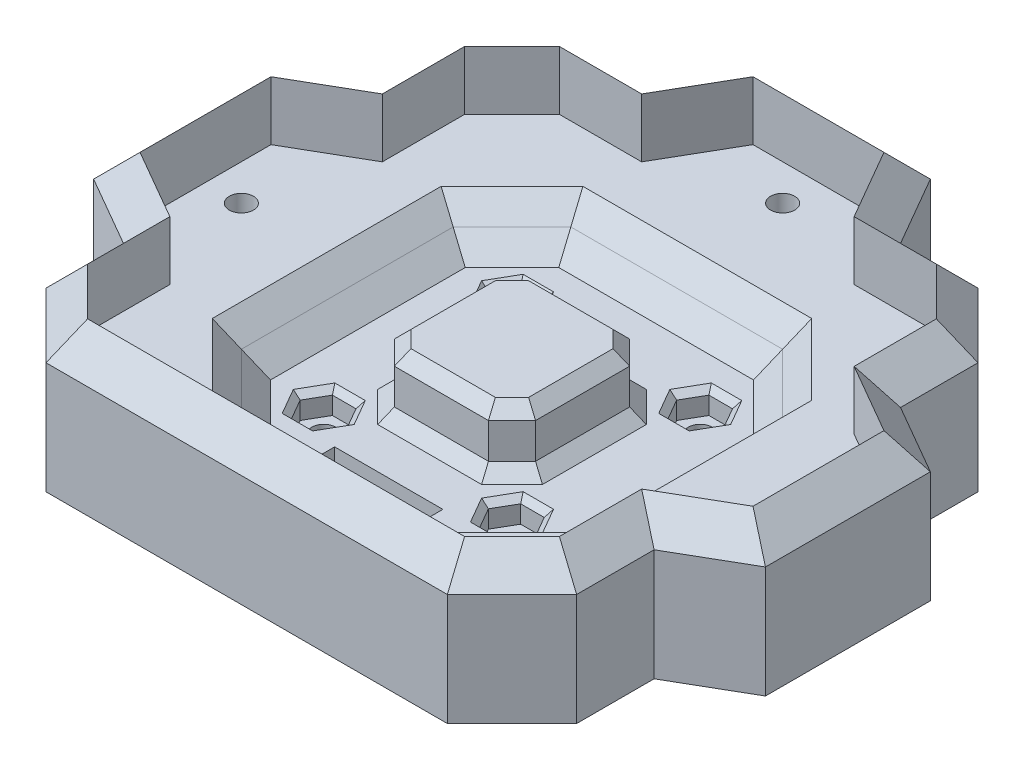
SolidWorks part; units mm, degrees
material "ABS"
ref_plane "Front Plane" through (0, 0, 0) normal (0, 0, 1) x (1, 0, 0)
ref_plane "Top Plane" through (0, 0, 0) normal (0, 1, 0) x (1, 0, 0)
ref_plane "Right Plane" through (0, 0, 0) normal (1, 0, 0) x (0, 0, -1)
sketch "Track Reference" plane through (0, 0, 0) normal (0, 1, 0) x (1, 0, 0)
  line L0 (-40, 32) -> (-32, 40)
  line L1 (-32, 40) -> (-18, 40)
  line L2 (-40, 32) -> (-40, 18)
  line L3 (-32, -40) -> (-5, -40)
  line L4 (40, 32) -> (40, 18)
  line L5 (-40, -32) -> (-32, -40)
  line L6 (32, -40) -> (40, -32)
  line L7 (32, 40) -> (40, 32)
  line L8 (-40, -18) -> (-52, -11.0718)
  line L9 (-52, -11.0718) -> (-52, 11.0718)
  line L10 (-52, 11.0718) -> (-40, 18)
  line L11 (-18, 40) -> (-11.0718, 52)
  line L12 (-11.0718, 52) -> (11.0718, 52)
  line L13 (11.0718, 52) -> (18, 40)
  line L14 (40, 18) -> (52, 11.0718)
  line L15 (52, 11.0718) -> (52, -11.0718)
  line L16 (52, -11.0718) -> (40, -18)
  line L17 (18, -40) -> (11.0718, -52)
  line L18 (11.0718, -52) -> (-11.0718, -52)
  line L19 (-11.0718, -52) -> (-18, -40)
  line L20 (-5, -27.65) -> (-5, -40)
  line L21 (-5, -27.65) -> (-9, -23.65)
  line L22 (-9, -23.65) -> (-9, -21.15)
  line L23 (-9, -21.15) -> (9, -21.15)
  line L24 (9, -21.15) -> (9, -23.65)
  line L25 (9, -23.65) -> (5, -27.65)
  line L26 (5, -27.65) -> (5, -40)
  line L27 (-40, 18) -> (-40, -18) construction
  line L28 (-40, -18) -> (-40, -32)
  line L29 (-18, 40) -> (18, 40) construction
  line L30 (18, 40) -> (32, 40)
  line L31 (40, 18) -> (40, -18) construction
  line L32 (40, -18) -> (40, -32)
  line L33 (-5, -40) -> (5, -40) construction
  line L34 (5, -40) -> (32, -40)
  circle A0 centre (-46, 0) radius 2.05
  circle A1 centre (0, 46) radius 2.05
  circle A2 centre (46, 0) radius 2.05
  circle A3 centre (0, -46) radius 2.05
  point P0 (-40, 40)
  point P1 (40, -40)
  point P2 (-40, -40)
  point P3 (40, 40)
  point P14 (-52, 0)
  point P22 (0, -21.15)
  point P23 (0, 0)
  point P25 (0, 0)
  point P44 (0, 0)
  point P51 (0, 0)
  point P52 (9, -19.8212)
  dimension "D8" = 4.1
  dimension "D1" = 80
  dimension "D2" = 80
  dimension "D3" = 8
  dimension "D4" = 8
  dimension "D5" = 60
  dimension "D6" = 12
  dimension "D7" = 36
  dimension "D9" = 6
  dimension "D12" = 18
  dimension "D11" = 10
  dimension "D13" = 2.5
  dimension "D14" = 45
  dimension "D15" = 18.85
  dimension "D10" = 4
sketch "Sketch2" plane through (0, 0, 0) normal (0, 1, 0) x (1, 0, 0)
  line L127 (-5, -40.1) -> (5, -40.1)
  line L128 (-5, -45.1) -> (5, -45.1)
  line L129 (5, -45.1) -> (34.1125, -45.1)
  line L130 (34.1125, -45.1) -> (45.1, -34.1125)
  line L131 (45.1, -34.1125) -> (45.1, -20.9445)
  line L132 (45.1, -20.9445) -> (57.1, -14.0163)
  line L133 (57.1, -14.0163) -> (57.1, 14.0163)
  line L134 (57.1, 14.0163) -> (45.1, 20.9445)
  line L135 (45.1, 20.9445) -> (45.1, 34.1125)
  line L136 (45.1, 34.1125) -> (34.1125, 45.1)
  line L137 (34.1125, 45.1) -> (20.9445, 45.1)
  line L138 (20.9445, 45.1) -> (14.0163, 57.1)
  line L139 (14.0163, 57.1) -> (-14.0163, 57.1)
  line L140 (-14.0163, 57.1) -> (-20.9445, 45.1)
  line L141 (-20.9445, 45.1) -> (-34.1125, 45.1)
  line L142 (-34.1125, 45.1) -> (-45.1, 34.1125)
  line L143 (-45.1, 34.1125) -> (-45.1, 20.9445)
  line L144 (-45.1, 20.9445) -> (-57.1, 14.0163)
  line L145 (-57.1, 14.0163) -> (-57.1, -14.0163)
  line L146 (-57.1, -14.0163) -> (-45.1, -20.9445)
  line L147 (-45.1, -20.9445) -> (-45.1, -34.1125)
  line L148 (11.1295, 52.1) -> (-11.1295, 52.1)
  line L149 (18.0577, 40.1) -> (11.1295, 52.1)
  line L150 (32.0414, 40.1) -> (18.0577, 40.1)
  line L151 (40.1, 32.0414) -> (32.0414, 40.1)
  line L152 (40.1, 18.0577) -> (40.1, 32.0414)
  line L153 (52.1, 11.1295) -> (40.1, 18.0577)
  line L154 (52.1, -11.1295) -> (52.1, 11.1295)
  line L155 (40.1, -18.0577) -> (52.1, -11.1295)
  line L156 (40.1, -32.0414) -> (40.1, -18.0577)
  line L157 (32.0414, -40.1) -> (40.1, -32.0414)
  line L158 (5, -40.1) -> (32.0414, -40.1)
  line L159 (-32.0414, -40.1) -> (-5, -40.1)
  line L160 (-40.1, -32.0414) -> (-32.0414, -40.1)
  line L161 (-40.1, -18.0577) -> (-40.1, -32.0414)
  line L162 (-52.1, -11.1295) -> (-40.1, -18.0577)
  line L163 (-52.1, 11.1295) -> (-52.1, -11.1295)
  line L164 (-40.1, 18.0577) -> (-52.1, 11.1295)
  line L165 (-40.1, 32.0414) -> (-40.1, 18.0577)
  line L166 (-32.0414, 40.1) -> (-40.1, 32.0414)
  line L167 (-18.0577, 40.1) -> (-32.0414, 40.1)
  line L168 (-11.1295, 52.1) -> (-18.0577, 40.1)
  line L169 (11.1295, 52.1) -> (-11.1295, 52.1)
  line L170 (18.0577, 40.1) -> (11.1295, 52.1)
  line L171 (32.0414, 40.1) -> (18.0577, 40.1)
  line L172 (40.1, 32.0414) -> (32.0414, 40.1)
  line L173 (40.1, 18.0577) -> (40.1, 32.0414)
  line L174 (52.1, 11.1295) -> (40.1, 18.0577)
  line L175 (52.1, -11.1295) -> (52.1, 11.1295)
  line L176 (40.1, -18.0577) -> (52.1, -11.1295)
  line L177 (40.1, -32.0414) -> (40.1, -18.0577)
  line L178 (32.0414, -40.1) -> (40.1, -32.0414)
  line L179 (5, -40.1) -> (32.0414, -40.1)
  line L180 (-32.0414, -40.1) -> (-5, -40.1)
  line L181 (-40.1, -32.0414) -> (-32.0414, -40.1)
  line L182 (-40.1, -18.0577) -> (-40.1, -32.0414)
  line L183 (-52.1, -11.1295) -> (-40.1, -18.0577)
  line L184 (-52.1, 11.1295) -> (-52.1, -11.1295)
  line L185 (-40.1, 18.0577) -> (-52.1, 11.1295)
  line L186 (-40.1, 32.0414) -> (-40.1, 18.0577)
  line L187 (-32.0414, 40.1) -> (-40.1, 32.0414)
  line L188 (-18.0577, 40.1) -> (-32.0414, 40.1)
  line L189 (-11.1295, 52.1) -> (-18.0577, 40.1)
  line L190 (-45.1, -34.1125) -> (-34.1125, -45.1)
  line L191 (-34.1125, -45.1) -> (-5, -45.1)
  dimension "D1" = 0.1
  dimension "D2" = 5
extrude "Outer Walls Extrude" add sketch "Sketch2" along normal blind 10
sketch "Sketch3" plane through (0, 0, 0) normal (0, -1, 0) x (1, 0, 0)
  line L20 (34.1125, 45.1) -> (-34.1125, 45.1)
  line L21 (-34.1125, 45.1) -> (-45.1, 34.1125)
  line L22 (-45.1, 34.1125) -> (-45.1, 20.9445)
  line L23 (-45.1, 20.9445) -> (-57.1, 14.0163)
  line L24 (-57.1, 14.0163) -> (-57.1, -14.0163)
  line L25 (-57.1, -14.0163) -> (-45.1, -20.9445)
  line L26 (-45.1, -20.9445) -> (-45.1, -34.1125)
  line L27 (-45.1, -34.1125) -> (-34.1125, -45.1)
  line L28 (-34.1125, -45.1) -> (-20.9445, -45.1)
  line L29 (-20.9445, -45.1) -> (-14.0163, -57.1)
  line L30 (-14.0163, -57.1) -> (14.0163, -57.1)
  line L31 (14.0163, -57.1) -> (20.9445, -45.1)
  line L32 (20.9445, -45.1) -> (34.1125, -45.1)
  line L33 (34.1125, -45.1) -> (45.1, -34.1125)
  line L34 (45.1, -34.1125) -> (45.1, -20.9445)
  line L35 (45.1, -20.9445) -> (57.1, -14.0163)
  line L36 (57.1, -14.0163) -> (57.1, 14.0163)
  line L37 (57.1, 14.0163) -> (45.1, 20.9445)
  line L38 (45.1, 20.9445) -> (45.1, 34.1125)
  line L39 (45.1, 34.1125) -> (34.1125, 45.1)
  line L40 (34.1125, 45.1) -> (-34.1125, 45.1)
  line L41 (-34.1125, 45.1) -> (-45.1, 34.1125)
  line L42 (-45.1, 34.1125) -> (-45.1, 20.9445)
  line L43 (-45.1, 20.9445) -> (-57.1, 14.0163)
  line L44 (-57.1, 14.0163) -> (-57.1, -14.0163)
  line L45 (-57.1, -14.0163) -> (-45.1, -20.9445)
  line L46 (-45.1, -20.9445) -> (-45.1, -34.1125)
  line L47 (-45.1, -34.1125) -> (-34.1125, -45.1)
  line L48 (-34.1125, -45.1) -> (-20.9445, -45.1)
  line L49 (-20.9445, -45.1) -> (-14.0163, -57.1)
  line L50 (-14.0163, -57.1) -> (14.0163, -57.1)
  line L51 (14.0163, -57.1) -> (20.9445, -45.1)
  line L52 (20.9445, -45.1) -> (34.1125, -45.1)
  line L53 (34.1125, -45.1) -> (45.1, -34.1125)
  line L54 (45.1, -34.1125) -> (45.1, -20.9445)
  line L55 (45.1, -20.9445) -> (57.1, -14.0163)
  line L56 (57.1, -14.0163) -> (57.1, 14.0163)
  line L57 (57.1, 14.0163) -> (45.1, 20.9445)
  line L58 (45.1, 20.9445) -> (45.1, 34.1125)
  line L59 (45.1, 34.1125) -> (34.1125, 45.1)
  dimension "D1" = 0
extrude "Base Extrude" add sketch "Sketch3" along normal blind 14
sketch "Sketch11" plane through (0, 0, 0) normal (0, 1, 0) x (1, 0, 0)
  line L15 (-5.2, -40) -> (-5.2, -40.1)
  line L16 (-32.0414, -40.1) -> (32.0414, -40.1) construction
  line L17 (5.2, -40) -> (5.2, -40.1)
  line L18 (5.2, -40.1) -> (-5.2, -40.1)
  line L22 (5.2, -40) -> (5.2, -27.7328)
  line L23 (5.2, -27.7328) -> (9.2, -23.7328)
  line L24 (9.2, -23.7328) -> (9.2, -20.95)
  line L25 (9.2, -20.95) -> (-9.2, -20.95)
  line L26 (-9.2, -20.95) -> (-9.2, -23.7328)
  line L27 (-9.2, -23.7328) -> (-5.2, -27.7328)
  line L28 (-5.2, -27.7328) -> (-5.2, -40)
  line L29 (5.2, -40) -> (5.2, -27.7328)
  line L30 (5.2, -27.7328) -> (9.2, -23.7328)
  line L31 (9.2, -23.7328) -> (9.2, -20.95)
  line L32 (9.2, -20.95) -> (-9.2, -20.95)
  line L33 (-9.2, -20.95) -> (-9.2, -23.7328)
  line L34 (-9.2, -23.7328) -> (-5.2, -27.7328)
  line L35 (-5.2, -27.7328) -> (-5.2, -40)
  dimension "D1" = 0.2
extrude "Rack Cut" cut sketch "Sketch11" against normal through all
chamfer "Walls Outer Chamfer" distance 5 angle 45 20 edges at (-39.6062, 10, 39.6062) (-45.1, 10, 27.5285) (-51.1, 10, 17.4804) (0, 10, 45.1) (39.6062, 10, 39.6062) (45.1, 10, 27.5285) (51.1, 10, 17.4804) (57.1, 10, 0) (51.1, 10, -17.4804) (45.1, 10, -27.5285) (39.6062, 10, -39.6062) (27.5285, 10, -45.1) (17.4804, 10, -51.1) (0, 10, -57.1) (-17.4804, 10, -51.1) (-27.5285, 10, -45.1) (-39.6062, 10, -39.6062) (-45.1, 10, -27.5285) (-51.1, 10, -17.4804) (-57.1, 10, 0)
sketch "Sketch6" plane through (0, 0, 0) normal (0, 1, 0) x (1, 0, 0)
  line L1 (18, -28) -> (-18, -28)
  line L2 (28, -18) -> (28, 18)
  line L3 (18, 28) -> (-18, 28)
  line L4 (-28, -18) -> (-28, 18)
  line L5 (-18, 28) -> (-28, 18)
  line L6 (-18, -28) -> (-28, -18)
  line L7 (28, -18) -> (18, -28)
  line L8 (28, 18) -> (18, 28)
  point P0 (0, 0)
  point P1 (-28, 0)
  point P2 (0, 0)
  point P3 (0, 0)
  point P4 (0, 0)
  point P14 (0, 0)
  point P15 (0, 28)
  point P16 (0, 0)
  point P17 (0, 0)
  dimension "D1" = 56
  dimension "D2" = 10
extrude "Spacer Cutout" cut sketch "Sketch6" against normal offset from surface (7 mm away) 7 up to face at (0, -14, 28.1289)
chamfer "Spacer Chamfer" distance 3.5 angle 45 18 edges at (11.6, -7, 28) (23, -7, 23) (28, -7, 0) (23, -7, -23) (0, -7, -28) (-11.6, -7, 28) (-23, -7, 23) (-28, -7, 0) (-23, -7, -23) (28, 0, 0) (23, 0, -23) (0, 0, -28) (23, 0, 23) (11.6, 0, 28) (-11.6, 0, 28) (-23, 0, 23) (-28, 0, 0) (-23, 0, -23)
sketch "Sketch12" plane through (0, -7, 0) normal (0, 1, 0) x (1, 0, 0)
  line L0 (-12, 8) -> (-8, 12)
  line L1 (-8, -12) -> (8, -12)
  line L2 (-12, -8) -> (-12, 8)
  line L3 (-8, 12) -> (8, 12)
  line L4 (12, -8) -> (12, 8)
  line L7 (-12, -8) -> (-8, -12)
  line L8 (8, -12) -> (12, -8)
  line L9 (8, 12) -> (12, 8)
  point P0 (0, 0)
  point P1 (0, 0)
  point P2 (0, 0)
  point P3 (0, 12)
  point P4 (-12, 0)
  point P14 (-7, 6.0719)
  dimension "D1" = 24
  dimension "D2" = 4
extrude "Bumper Extrude" add sketch "Sketch12" along normal blind 10
chamfer "Bumper Chamfer" distance 2 angle 45 16 edges at (-10, 3, -10) (0, 3, -12) (10, 3, -10) (12, 3, 0) (10, 3, 10) (0, 3, 12) (-10, 3, 10) (-12, 3, 0) (-10, -7, -10) (0, -7, -12) (10, -7, -10) (12, -7, 0) (10, -7, 10) (0, -7, 12) (-12, -7, 0) (-10, -7, 10)
sketch "Sketch5" plane through (0, 0, 0) normal (0, 1, 0) x (1, 0, 0)
  circle A0 centre (46, 0) radius 2.05 construction
  circle A1 centre (0, 46) radius 2.05 construction
  circle A2 centre (-46, 0) radius 2.05 construction
  circle A3 centre (46, 0) radius 2.05
  circle A4 centre (0, 46) radius 2.05
  circle A5 centre (-46, 0) radius 2.05
extrude "Track Mount Holes" cut sketch "Sketch5" against normal through all
sketch "Sketch10" plane through (0, -14, 0) normal (0, -1, 0) x (1, 0, 0)
  circle A0 centre (-46, 0) radius 3.5
  circle A1 centre (0, -46) radius 3.5
  circle A2 centre (46, 0) radius 3.5
  dimension "D1" = 7
extrude "Track Mount Countersink" cut sketch "Sketch10" against normal blind 3
chamfer "Track Mount Countersink Chamfer" distance 1.5 angle 45 6 edges at (46, -14, -3.5) (0, -14, -49.5) (-46, -14, -3.5) (46, -11, -2.05) (0, -11, -48.05) (-46, -11, -2.05)
sketch "Sketch7" plane through (0, -7, 0) normal (0, 1, 0) x (1, 0, 0)
  line L1 (16, -16) -> (-16, -16) construction
  line L2 (16, -16) -> (16, 16) construction
  line L3 (16, 16) -> (-16, 16) construction
  line L4 (-16, -16) -> (-16, 16) construction
  line L5 (16, -16) -> (-16, 16) construction
  line L6 (16, 16) -> (-16, -16) construction
  circle A0 centre (-16, 16) radius 2.05
  circle A1 centre (16, 16) radius 2.05
  circle A2 centre (16, -16) radius 2.05
  circle A3 centre (-16, -16) radius 2.05
  point P0 (0, 0)
  dimension "D2" = 4.1
  dimension "D1" = 32
extrude "Floor Mount Holes" cut sketch "Sketch7" against normal through all
sketch "Sketch9" plane through (0, -7, 0) normal (0, 1, 0) x (1, 0, 0)
  line L1 (-11.9874, 16) -> (-13.9937, 19.475)
  line L2 (-13.9937, 19.475) -> (-18.0063, 19.475)
  line L3 (-18.0063, 19.475) -> (-20.0126, 16)
  line L4 (-20.0126, 16) -> (-18.0063, 12.525)
  line L5 (-18.0063, 12.525) -> (-13.9937, 12.525)
  line L6 (-13.9937, 12.525) -> (-11.9874, 16)
  line L7 (11.9874, 16) -> (13.9937, 12.525)
  line L8 (13.9937, 12.525) -> (18.0063, 12.525)
  line L9 (18.0063, 12.525) -> (20.0126, 16)
  line L10 (20.0126, 16) -> (18.0063, 19.475)
  line L11 (18.0063, 19.475) -> (13.9937, 19.475)
  line L12 (13.9937, 19.475) -> (11.9874, 16)
  line L13 (-11.9874, -16) -> (-13.9937, -12.525)
  line L14 (-13.9937, -12.525) -> (-18.0063, -12.525)
  line L15 (-18.0063, -12.525) -> (-20.0126, -16)
  line L16 (-20.0126, -16) -> (-18.0063, -19.475)
  line L17 (-18.0063, -19.475) -> (-13.9937, -19.475)
  line L18 (-13.9937, -19.475) -> (-11.9874, -16)
  line L19 (11.9874, -16) -> (13.9937, -19.475)
  line L20 (13.9937, -19.475) -> (18.0063, -19.475)
  line L21 (18.0063, -19.475) -> (20.0126, -16)
  line L22 (20.0126, -16) -> (18.0063, -12.525)
  line L23 (18.0063, -12.525) -> (13.9937, -12.525)
  line L24 (13.9937, -12.525) -> (11.9874, -16)
  circle A0 centre (-16, 16) radius 3.475 construction
  circle A1 centre (16, 16) radius 3.475 construction
  circle A2 centre (-16, -16) radius 3.475 construction
  circle A3 centre (16, -16) radius 3.475 construction
  dimension "D1" = 6.95
extrude "Floor Mount Nut Inset" cut sketch "Sketch9" against normal blind 4
chamfer "Floor Mount Nut Chamfer" distance 1 angle 45 24 edges at (16, -7, 19.475) (19.0094, -7, 17.7375) (19.0094, -7, 14.2625) (12.9906, -7, 17.7375) (12.9906, -7, 14.2625) (16, -7, 12.525) (-19.0094, -7, 14.2625) (-19.0094, -7, 17.7375) (-16, -7, 19.475) (-12.9906, -7, 17.7375) (-12.9906, -7, 14.2625) (-16, -7, 12.525) (16, -7, -12.525) (19.0094, -7, -14.2625) (19.0094, -7, -17.7375) (12.9906, -7, -14.2625) (12.9906, -7, -17.7375) (16, -7, -19.475) (-19.0094, -7, -17.7375) (-19.0094, -7, -14.2625) (-16, -7, -12.525) (-12.9906, -7, -14.2625) (-12.9906, -7, -17.7375) (-16, -7, -19.475)
equation "\"D2@Track Reference\"=\"D1@Track Reference\""
